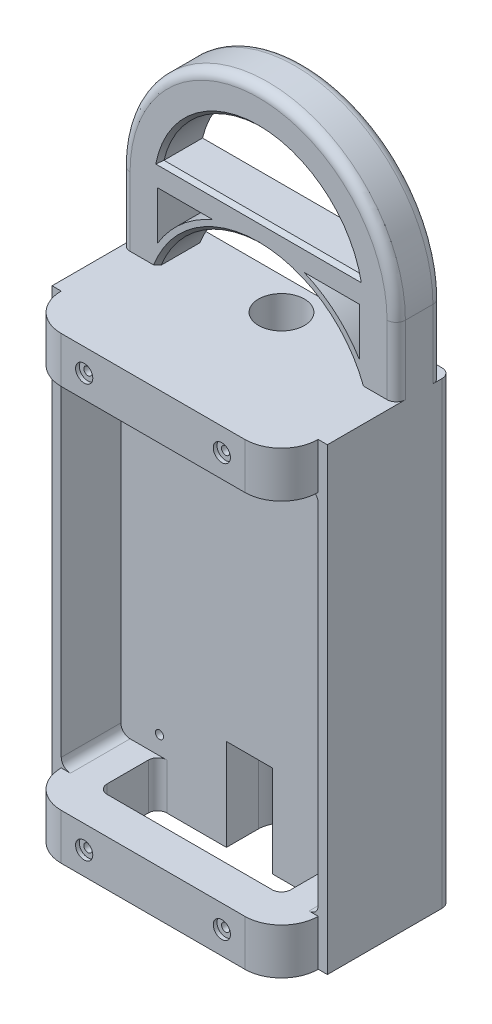
SolidWorks part; units mm, degrees
material "6061 Alloy"
ref_plane "Front Plane" through (0, 0, 0) normal (0, 0, 1) x (1, 0, 0)
ref_plane "Top Plane" through (0, 0, 0) normal (0, 1, 0) x (1, 0, 0)
ref_plane "Right Plane" through (0, 0, 0) normal (1, 0, 0) x (0, 0, -1)
sketch "Sketch1" plane through (0, 0, 0) normal (0, 1, 0) x (1, 0, 0)
  line L1 (-38.1, 38.1) -> (38.1, 38.1)
  line L2 (-38.1, 38.1) -> (-38.1, -38.1)
  line L3 (-38.1, -38.1) -> (38.1, -38.1)
  line L4 (38.1, 38.1) -> (38.1, -38.1)
  line L5 (-38.1, 38.1) -> (38.1, -38.1) construction
  line L6 (-38.1, -38.1) -> (38.1, 38.1) construction
  point P0 (0, 0)
  dimension "D1" = 76.2
  dimension "D2" = 76.2
extrude "Boss-Extrude1" add sketch "Sketch1" along normal blind 127
sketch "Sketch2" plane through (0, 127, 0) normal (0, 1, 0) x (1, 0, 0)
  line L0 (-38.1, 6.35) -> (38.1, 6.35)
  line L1 (-38.1, 38.1) -> (-38.1, -38.1) construction
  line L2 (38.1, -38.1) -> (38.1, 38.1) construction
  line L3 (-38.1, -6.35) -> (38.1, -6.35)
  line L4 (-38.1, 6.35) -> (-38.1, -6.35)
  line L5 (38.1, 6.35) -> (38.1, -6.35)
  dimension "D1" = 6.35
  dimension "D2" = 6.35
fillet "Fillet1" radius 12.7 4 edges at (38.1, 63.5, 38.1) (38.1, 63.5, -38.1) (-38.1, 63.5, -38.1) (-38.1, 63.5, 38.1)
extrude "Boss-Extrude6" add sketch "Sketch2" along normal blind 57.15
sketch "Sketch5" plane through (0, 0, 6.35) normal (0, 0, 1) x (1, 0, 0)
  line L0 (-27.94, 127) -> (27.94, 127)
  line L1 (0, 184.15) -> (0, 146.05)
  line L4 (-38.1, 184.15) -> (38.1, 184.15) construction
  line L5 (-38.1, 184.15) -> (-38.1, 127) construction
  line L6 (38.1, 184.15) -> (38.1, 127) construction
  line L7 (-38.1, 146.05) -> (-27.94, 146.05)
  line L8 (27.94, 146.05) -> (27.94, 127)
  line L9 (-38.1, 127) -> (38.1, 127) construction
  line L10 (27.94, 127) -> (38.1, 127)
  line L11 (38.1, 127) -> (38.1, 146.05)
  line L12 (-38.1, 146.05) -> (-38.1, 127)
  line L13 (-38.1, 127) -> (-27.94, 127)
  line L14 (-27.94, 127) -> (-27.94, 146.05)
  line L15 (-27.94, 146.05) -> (27.94, 146.05)
  line L16 (0, 146.05) -> (0, 152.4937)
  line L17 (0, 152.4937) -> (27.1868, 152.4937)
  line L18 (0, 152.4937) -> (-27.1868, 152.4937)
  arc A0 (-38.1, 146.05) -> (38.1, 146.05) centre (0, 146.05) cw
  arc A1 (-27.94, 146.05) -> (27.94, 146.05) centre (0, 146.05) cw
  arc A2 (-27.94, 146.05) -> (-27.1868, 152.4937) centre (0, 146.05) cw
  arc A3 (27.94, 146.05) -> (27.1868, 152.4937) centre (0, 146.05) ccw
  arc A4 (0, 146.05) -> (-27.94, 127) centre (0, 116.0357) ccw
  arc A5 (0, 146.05) -> (27.94, 127) centre (0, 116.0357) cw
  arc A6 (0, 148.59) -> (-30.3045, 127.9279) centre (0, 116.0357) ccw
  arc A7 (0, 148.59) -> (30.3045, 127.9279) centre (0, 116.0357) cw
  line M8 (-38.1, 127) -> (38.1, 127)
  line M9 (38.1, 127) -> (38.1, 184.15)
  line M10 (38.1, 184.15) -> (-38.1, 184.15)
  line M11 (-38.1, 184.15) -> (-38.1, 127)
  dimension "D3" = 2.54
  dimension "D4" = 2.54
  dimension "D1" = 38.1
  dimension "D2" = 10.16
extrude "Cut-Extrude2" cut sketch "Sketch5" against normal blind 12.7 contours A0 M11 M10 | A1 L18 L1 | A1 L1 L17 | A6 L15 L14 | L15 A7 L8 | A5 A4 M8 | A0 M10 M9 region at (0, 134.8748, 6.35) region at (-23.417, 142.0913, 6.35) region at (23.417, 142.0913, 6.35) region at (-29.5897, 175.6397, 6.35) region at (29.5897, 175.6397, 6.35) region at (-11.0421, 161.459, 6.35) region at (11.0421, 161.459, 6.35)
sketch "Sketch6" plane through (0, 0, 0) normal (0, -1, 0) x (1, 0, 0)
  line L0 (-38.1, 25.4) -> (38.1, 25.4)
  line L1 (-25.4, 25.4) -> (-25.4, 8.89)
  line L2 (25.4, 25.4) -> (25.4, 8.89)
  line L16 (-35.56, 8.89) -> (35.56, 8.89)
  line L17 (-35.56, -8.89) -> (35.56, -8.89)
  line L20 (-35.56, 25.4) -> (-35.56, -25.4)
  line L21 (-25.4, -35.56) -> (25.4, -35.56)
  line L22 (35.56, -25.4) -> (35.56, 25.4)
  line L23 (25.4, 35.56) -> (-25.4, 35.56)
  line L24 (-35.56, 25.4) -> (-35.56, -25.4)
  line L25 (-25.4, -35.56) -> (25.4, -35.56)
  line L26 (35.56, -25.4) -> (35.56, 25.4)
  line L27 (25.4, 35.56) -> (-25.4, 35.56)
  circle A0 centre (0, 0) radius 6.35
  arc A25 (-35.56, -25.4) -> (-25.4, -35.56) centre (-25.4, -25.4) ccw
  arc A26 (25.4, -35.56) -> (35.56, -25.4) centre (25.4, -25.4) ccw
  arc A27 (35.56, 25.4) -> (25.4, 35.56) centre (25.4, 25.4) ccw
  arc A28 (-25.4, 35.56) -> (-35.56, 25.4) centre (-25.4, 25.4) ccw
  arc A29 (-35.56, -25.4) -> (-25.4, -35.56) centre (-25.4, -25.4) ccw
  arc A30 (25.4, -35.56) -> (35.56, -25.4) centre (25.4, -25.4) ccw
  arc A31 (35.56, 25.4) -> (25.4, 35.56) centre (25.4, 25.4) ccw
  arc A32 (-25.4, 35.56) -> (-35.56, 25.4) centre (-25.4, 25.4) ccw
  point P5 (0, 8.89)
  arc M12 (38.1, 25.4) -> (25.4, 38.1) centre (25.4, 25.4) ccw
  line M13 (25.4, 38.1) -> (-25.4, 38.1)
  arc M14 (-25.4, 38.1) -> (-38.1, 25.4) centre (-25.4, 25.4) ccw
  dimension "D1" = 12.7
  dimension "D3" = 8.89
  dimension "D4" = 8.89
  dimension "D5" = 16.51
  dimension "D6" = 76.2
  dimension "D2" = 2.54
extrude "Cut-Extrude7" cut sketch "Sketch6" against normal blind 127 contours A32 L27 A31 L0 M12 M13 M14 region at (-33.834, 0, 33.834)
extrude "Cut-Extrude8" cut sketch "Sketch6<7>" against normal blind 114.3 contours L27 A32 L0 A31 region at (0, 0, 30.2964)
sketch "Sketch6<7>" plane through (0, 0, 0) normal (0, -1, 0) x (1, 0, 0) same geometry as "Sketch6"
extrude "Cut-Extrude9" cut sketch "Sketch6<8>" against normal blind 124.46 contours L25 A30 L26 L17 L24 A29 region at (0, 0, -21.9603)
sketch "Sketch6<8>" plane through (0, 0, 0) normal (0, -1, 0) x (1, 0, 0) same geometry as "Sketch6"
extrude "Cut-Extrude10" cut sketch "Sketch6<9>" against normal blind 114.3 contours L0 L24 L16 L1 | L16 L26 L0 L2 region at (-30.48, 0, 17.145) region at (30.48, 0, 17.145)
sketch "Sketch6<9>" plane through (0, 0, 0) normal (0, -1, 0) x (1, 0, 0) same geometry as "Sketch6"
extrude "Cut-Extrude11" cut sketch "Sketch6<10>" against normal blind 124.46 contours L1 L16 L2 L0 region at (0, 0, 17.145)
sketch "Sketch6<10>" plane through (0, 0, 0) normal (0, -1, 0) x (1, 0, 0) same geometry as "Sketch6"
extrude "Cut-Extrude12" cut sketch "Sketch6<12>" against normal blind 127 contours A0 region at (0, 0, 0)
sketch "Sketch6<12>" plane through (0, 0, 0) normal (0, -1, 0) x (1, 0, 0) same geometry as "Sketch6"
extrude "Boss-Extrude7" add sketch "Sketch6<13>" against normal blind 12.7 contours L0 L24 L16 L1 | L16 L26 L0 L2 region at (-30.48, 0, 17.145) region at (30.48, 0, 17.145)
sketch "Sketch6<13>" plane through (0, 0, 0) normal (0, -1, 0) x (1, 0, 0) same geometry as "Sketch6"
extrude "Boss-Extrude8" add sketch "Sketch6<14>" against normal blind 12.7 contours L27 A32 L0 A31 region at (0, 0, 30.2964)
sketch "Sketch6<14>" plane through (0, 0, 0) normal (0, -1, 0) x (1, 0, 0) same geometry as "Sketch6"
sketch "Sketch7" plane through (0, 0, 35.56) normal (0, 0, 1) x (1, 0, 0)
  line L0 (25.4, 127) -> (-25.4, 127) construction
  line L1 (-25.4, 127) -> (-25.4, 114.3) construction
  line L2 (25.4, 127) -> (25.4, 114.3) construction
  line L3 (25.4, 12.7) -> (-25.4, 12.7) construction
  line L4 (25.4, 12.7) -> (25.4, 0) construction
  point P0 (-19.05, 120.65)
  point P5 (19.05, 120.65)
  point P8 (-19.05, 6.35)
  point P11 (19.05, 6.35)
  dimension "D1" = 6.35
  dimension "D2" = 6.35
  dimension "D3" = 6.35
  dimension "D4" = 6.35
  dimension "D5" = 6.35
hole_wizard "CBORE for #1 Binding Head Machine Screw1" positions "Sketch7" profile "Sketch8" counterbore size "#1" standard "ANSI Inch"
sketch "Sketch8" plane through (-19.05, 120.65, 35.56) normal (1, 0, 0) x (0, -1, 0)
  line L0 (0, 0) -> (0, 8.2992)
  line L1 (0, 8.2992) -> (1.1303, 7.62)
  line L2 (1.1303, 7.62) -> (1.1303, 1.0414)
  line L3 (1.1303, 1.0414) -> (2.3812, 1.0414)
  line L4 (2.3812, 1.0414) -> (2.3812, 0)
  line L5 (2.3812, 0) -> (0, 0)
  line L10 (0, 8.2992) -> (-1.1303, 7.62) construction
  line L11 (0, -6.35) -> (0, 107.95) construction
  dimension "Hole Dia." = 2.2606
  dimension "Hole Depth" = 7.62
  dimension "C'Bore Dia." = 4.7625
  dimension "C'Bore Depth" = 1.0414
  dimension "Drill Angle" = 118
sketch "Sketch9" plane through (0, 0, 0) normal (0, -1, 0) x (1, 0, 0)
  line L0 (-35.56, -8.89) -> (-38.1, -8.89)
  line L1 (-38.1, -25.4) -> (-38.1, 25.4) construction
  line L2 (-38.1, -8.89) -> (-38.1, -39.4543)
  line L3 (-38.1, -39.4543) -> (40.8478, -39.4543)
  line L4 (40.8478, -39.4543) -> (40.8478, -8.89)
  line L5 (40.8478, -8.89) -> (-35.56, -8.89)
extrude "Cut-Extrude13" cut sketch "Sketch9" against normal blind 127
fillet "Fillet5" radius 2.54 2 edges at (-38.1, 63.5, -8.89) (38.1, 63.5, -8.89)
fillet "Fillet6" radius 2.54 6 edges at (-38.1, 136.525, 6.35) (38.1, 136.525, 6.35) (-38.1, 136.525, -6.35) (38.1, 136.525, -6.35) (0, 184.15, 6.35) (0, 184.15, -6.35)
chamfer "Chamfer1" distance 1.016 angle 45 4 edges at (0, 152.4937, -6.35) (0, 173.99, -6.35) (0, 173.99, 6.35) (0, 152.4937, 6.35)
chamfer "Chamfer2" distance 1.016 angle 45 2 edges at (0, 146.05, -6.35) (0, 146.05, 6.35)
sketch "Sketch10" plane through (0, 0, 0) normal (0, -1, 0) x (1, 0, 0)
  line L3 (-25.4, 8.89) -> (25.4, 8.89) construction
  line L4 (6.35, 8.89) -> (-6.35, 8.89)
  line L5 (-6.35, 8.89) -> (-6.35, 0)
  line L6 (6.35, 8.89) -> (6.35, 0)
  circle A0 centre (0, 0) radius 6.35 construction
  arc A1 (-6.35, 0) -> (6.35, 0) centre (0, 0) ccw
extrude "Cut-Extrude14" cut sketch "Sketch10" against normal blind 25.4
fillet "Fillet7" radius 2.54 4 edges at (25.4, 6.35, 8.89) (25.4, 6.35, 25.4) (-25.4, 6.35, 25.4) (-25.4, 6.35, 8.89)
fillet "Fillet8" radius 2.54 4 edges at (25.4, 119.38, 8.89) (25.4, 119.38, 25.4) (-25.4, 119.38, 25.4) (-25.4, 119.38, 8.89)
fillet "Fillet9" radius 2.54 4 edges at (35.56, 12.7, 17.145) (-35.56, 12.7, 17.145) (35.56, 114.3, 17.145) (-35.56, 114.3, 17.145)
sketch "Sketch11" plane through (0, 0, 8.89) normal (0, 0, 1) x (1, 0, 0)
  line L0 (-35.56, 114.3) -> (-25.4, 114.3) construction
  line L1 (-35.56, 111.76) -> (-35.56, 15.24) construction
  line L2 (35.56, 111.76) -> (35.56, 15.24) construction
  line L3 (-33.02, 12.7) -> (-22.86, 12.7) construction
  point P0 (-24.892, 109.22)
  point P5 (24.892, 109.22)
  point P8 (-24.892, 17.78)
  point P11 (24.892, 17.78)
  dimension "D1" = 5.08
  dimension "D2" = 10.668
  dimension "D3" = 10.668
  dimension "D4" = 5.08
hole_wizard "#4-40 Tapped Hole1" positions "Sketch11" profile "Sketch12" tap size "#4-40" standard "ANSI Inch"
sketch "Sketch12" plane through (-24.892, 109.22, 8.89) normal (1, 0, 0) x (0, -1, 0)
  line L0 (0, 0) -> (0, 2.9652)
  line L1 (0, 2.9652) -> (1.1303, 2.286)
  line L2 (1.1303, 2.286) -> (1.1303, 0)
  line L5 (1.1303, 0) -> (0, 0)
  line L10 (0, 2.9652) -> (-1.1303, 2.286) construction
  line L11 (0, -6.35) -> (0, 107.95) construction
  dimension "Tap Drill Dia." = 2.2606
  dimension "Tap Drill Depth" = 2.286
  dimension "Drill Angle" = 118
cosmetic thread "Hole Thread1" parameters "D1"=5.588, "D2"=2.8448
cosmetic thread "Hole Thread2" parameters "D1"=5.588, "D2"=2.8448
cosmetic thread "Hole Thread3" parameters "D1"=5.588, "D2"=2.8448
cosmetic thread "Hole Thread4" parameters "D1"=5.588, "D2"=2.8448
